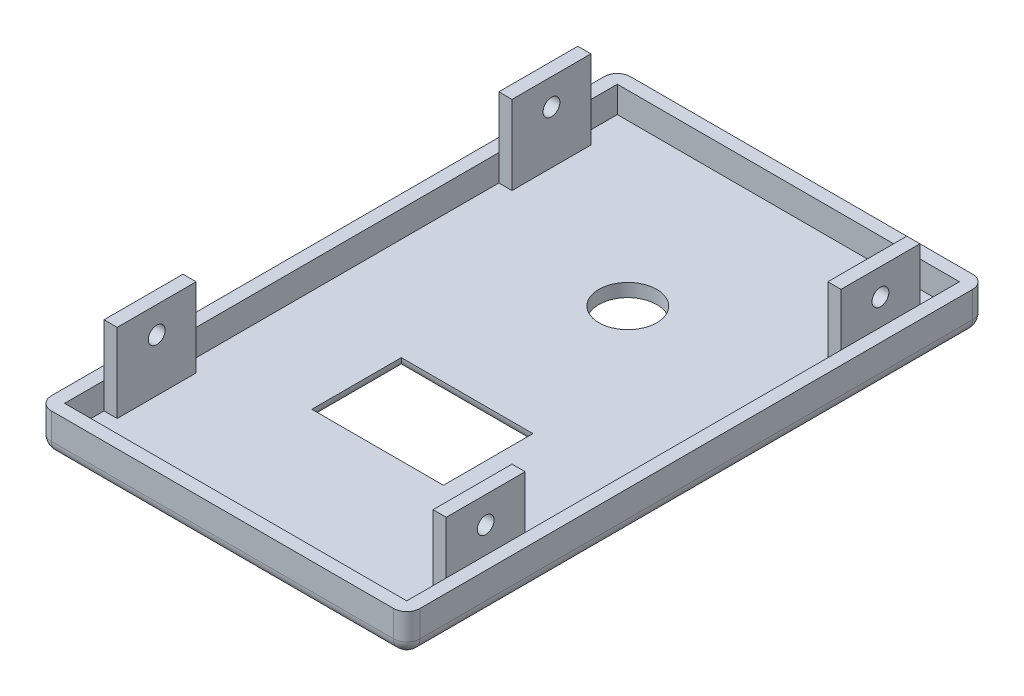
SolidWorks part; units mm, degrees
ref_plane "Front Plane" through (0, 0, 0) normal (0, 0, 1) x (1, 0, 0)
ref_plane "Top Plane" through (0, 0, 0) normal (0, 1, 0) x (1, 0, 0)
ref_plane "Right Plane" through (0, 0, 0) normal (1, 0, 0) x (0, 0, -1)
sketch "Sketch2" plane through (0, 0, 0) normal (0, 1, 0) x (1, 0, 0)
  line L1 (35, -55) -> (-35, -55)
  line L2 (35, -55) -> (35, 55)
  line L3 (35, 55) -> (-35, 55)
  line L4 (-35, -55) -> (-35, 55)
  line L5 (35, -55) -> (-35, 55) construction
  line L6 (35, 55) -> (-35, -55) construction
  point P0 (0, 0)
  dimension "D1" = 70
  dimension "D2" = 110
extrude "Boss-Extrude1" add sketch "Sketch2" along normal blind 2.5
sketch "Sketch3" plane through (0, 2.5, 0) normal (0, 1, 0) x (1, 0, 0)
  line L0 (35, 55) -> (-35, 55) construction
  line L1 (-35, -55) -> (-32.5, -55)
  line L2 (-35, -55) -> (-35, 55)
  line L3 (-35, 55) -> (-32.5, 55)
  line L4 (-32.5, -55) -> (-32.5, 55)
  line L5 (35, -55) -> (35, 55) construction
  line L6 (-32.5, 55) -> (35, 55)
  line L7 (-32.5, 55) -> (-32.5, 52.5)
  line L8 (-32.5, 52.5) -> (35, 52.5)
  line L9 (35, 55) -> (35, 52.5)
  line L10 (-35, -55) -> (35, -55) construction
  line L11 (35, 52.5) -> (32.5, 52.5)
  line L12 (35, 52.5) -> (35, -55)
  line L13 (35, -55) -> (32.5, -55)
  line L14 (32.5, 52.5) -> (32.5, -55)
  line L16 (-32.5, -55) -> (32.5, -55)
  line L17 (-32.5, -55) -> (-32.5, -52.5)
  line L18 (-32.5, -52.5) -> (32.5, -52.5)
  line L19 (32.5, -55) -> (32.5, -52.5)
  line M9 (-35, 55) -> (-35, -55)
  line M10 (-35, -55) -> (35, -55)
  line M11 (35, -55) -> (35, 55)
  line M12 (35, 55) -> (-35, 55)
  dimension "D1" = 2.5
  dimension "D2" = 2.5
  dimension "D3" = 2.5
  dimension "D4" = 2.5
extrude "Boss-Extrude2" add sketch "Sketch3" along normal blind 5 contours L4 M10 M12 M9 | L4 L8 M11 M12 | L8 L14 M10 M11 | L18 L4 L14 M10 region at (-33.75, 2.5, 0) region at (0, 2.5, 53.75) region at (33.75, 2.5, 1.25) region at (1.25, 2.5, -53.75)
sketch "Sketch4" plane through (0, 2.5, 0) normal (0, 1, 0) x (1, 0, 0)
  line L0 (-32.5, -52.5) -> (-32.5, 52.5) construction
  line L1 (-32.5, 45) -> (-30, 45)
  line L2 (-32.5, 45) -> (-32.5, 30)
  line L3 (-32.5, 30) -> (-30, 30)
  line L4 (-30, 45) -> (-30, 30)
  line L5 (-32.5, 52.5) -> (32.5, 52.5) construction
  line L6 (0, 52.5) -> (0, -48.0244) construction
  line L7 (32.5, 0) -> (-32.5, 0) construction
  line L8 (32.5, 52.5) -> (32.5, -52.5) construction
  line L9 (32.5, 45) -> (30, 45)
  line L10 (30, 45) -> (30, 30)
  line L11 (32.5, 30) -> (30, 30)
  line L12 (-32.5, -30) -> (-30, -30)
  line L13 (-30, -45) -> (-30, -30)
  line L14 (-32.5, -45) -> (-30, -45)
  line L15 (32.5, -45) -> (30, -45)
  line L16 (30, -45) -> (30, -30)
  line L17 (32.5, -30) -> (30, -30)
  line M10 (32.5, -52.5) -> (32.5, 52.5)
  line M12 (-32.5, 52.5) -> (-32.5, -52.5)
  dimension "D1" = 2.5
  dimension "D2" = 7.5
  dimension "D3" = 15
extrude "Boss-Extrude3" add sketch "Sketch4" along normal blind 15 contours L4 L1 L3 M12 | L11 L9 L10 M10 | L17 L16 L15 M10 | L14 L13 L12 M12 region at (-31.25, 2.5, 37.5) region at (-31.25, 2.5, -37.5) region at (31.25, 2.5, -37.5) region at (31.25, 2.5, 37.5)
sketch "Sketch6" plane through (-32.5, 0, 0) normal (-1, 0, 0) x (0, 0, 1)
  line L0 (-30, 7.5) -> (-45, 7.5) construction
  line L2 (-45, 17.5) -> (-45, 7.5) construction
  line L3 (0, 0) -> (0, 7.5) construction
  line L4 (-55, 7.5) -> (55, 7.5) construction
  circle A0 centre (-37.5, 12.5) radius 1.6
  circle A1 centre (37.5, 12.5) radius 1.6
  dimension "D3" = 3.2
  dimension "D1" = 5
  dimension "D2" = 7.5
extrude "Cut-Extrude1" cut sketch "Sketch6" against normal through all contours A0 | A1 region at (-32.5, 12.5, -37.5) region at (-32.5, 12.5, 37.5)
sketch "Sketch7" plane through (0, 0, 0) normal (0, -1, 0) x (1, 0, 0)
  line L0 (-35, 55) -> (35, 55) construction
  line L1 (-13.03, 25) -> (11.97, 25)
  line L2 (-13.03, 25) -> (-13.03, 8)
  line L3 (-13.03, 8) -> (11.97, 8)
  line L4 (11.97, 25) -> (11.97, 8)
  line L5 (-13.03, 25) -> (11.97, 8) construction
  line L6 (-13.03, 8) -> (11.97, 25) construction
  line L7 (35, 55) -> (35, -55) construction
  line L8 (-35, -55) -> (-35, 55) construction
  circle A0 centre (0, -22) radius 5.5
  point P0 (-0.53, 16.5)
  dimension "D5" = 11
  dimension "D1" = 17
  dimension "D2" = 25
  dimension "D3" = 30
  dimension "D4" = 23.03
  dimension "D6" = 30
  dimension "D7" = 35
extrude "Cut-Extrude2" cut sketch "Sketch7" against normal through all contours L4 L1 L2 L3 | A0 region at (-0.53, 0, 16.5) region at (0, 0, -22)
fillet "Fillet1" radius 2.5 4 edges at (-0.53, 0, 25) (11.97, 0, 16.5) (-0.53, 0, 8) (-13.03, 0, 16.5)
fillet "Fillet2" radius 2.5 8 edges at (35, 3.75, -55) (-35, 3.75, -55) (-35, 3.75, 55) (35, 3.75, 55) (0, 0, 55) (35, 0, 0) (0, 0, -55) (-35, 0, 0)
